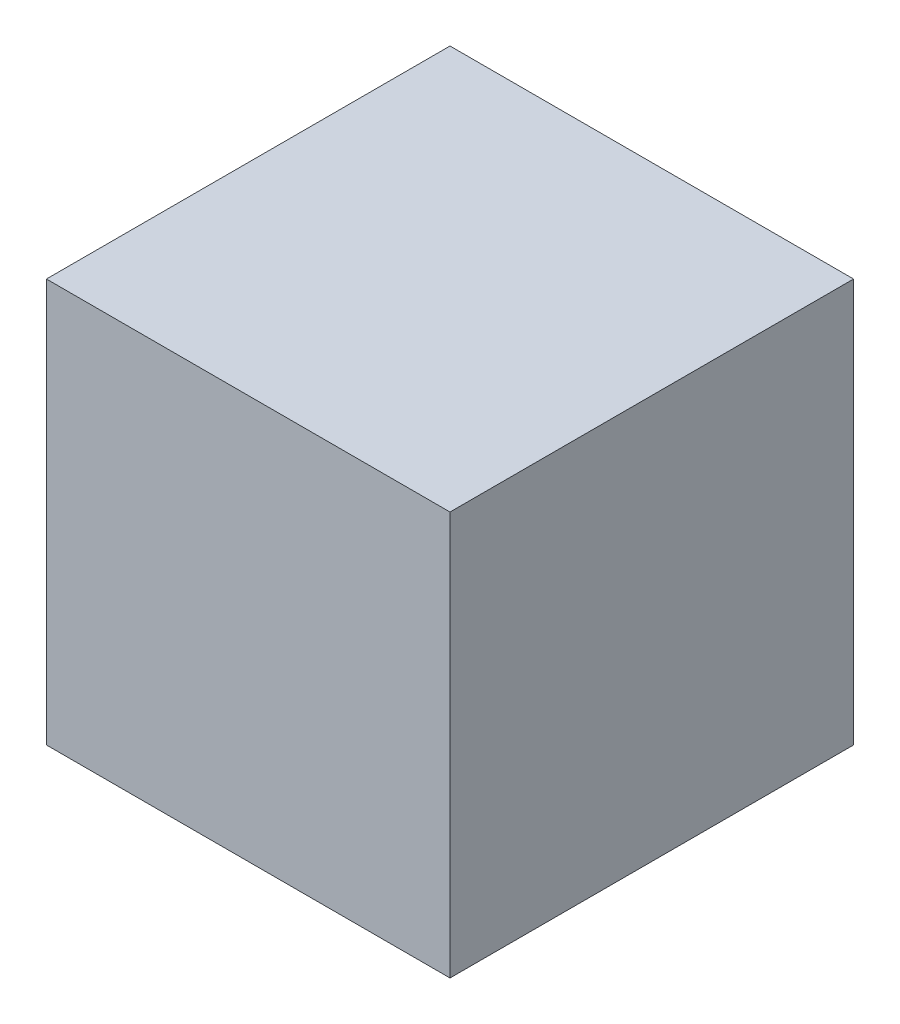
SolidWorks part; units mm, degrees
ref_plane "Front Plane" through (0, 0, 0) normal (0, 0, 1) x (1, 0, 0)
ref_plane "Top Plane" through (0, 0, 0) normal (0, 1, 0) x (1, 0, 0)
ref_plane "Right Plane" through (0, 0, 0) normal (1, 0, 0) x (0, 0, -1)
sketch "Sketch1" plane through (0, 0, 0) normal (0, 0, 1) x (1, 0, 0)
  line L1 (-25.4, -25.4) -> (25.4, -25.4)
  line L2 (-25.4, -25.4) -> (-25.4, 25.4)
  line L3 (-25.4, 25.4) -> (25.4, 25.4)
  line L4 (25.4, -25.4) -> (25.4, 25.4)
  line L5 (-25.4, -25.4) -> (25.4, 25.4) construction
  line L6 (-25.4, 25.4) -> (25.4, -25.4) construction
  point P0 (0, 0)
  dimension "D1" = 50.8
extrude "Boss-Extrude1" add sketch "Sketch1" along normal mid plane 50.8
sketch "Sketch2" plane through (0, -25.4, 0) normal (0, -1, 0) x (-1, 0, 0)
  circle A0 centre (0, 0) radius 18.92
  dimension "D1" = 37.84
extrude "Cut-Extrude2" cut sketch "Sketch2" against normal blind 10
shell "Shell1" thickness 10 removed face at (0, -15.4, -18.92)
sketch "Sketch3" plane through (-25.4, 0, 0) normal (-1, 0, 0) x (0, 0, 1)
  circle A0 centre (0, 0) radius 19.05
  dimension "D1" = 38.1
extrude "Cut-Extrude1" cut sketch "Sketch3" against normal blind 25.4
